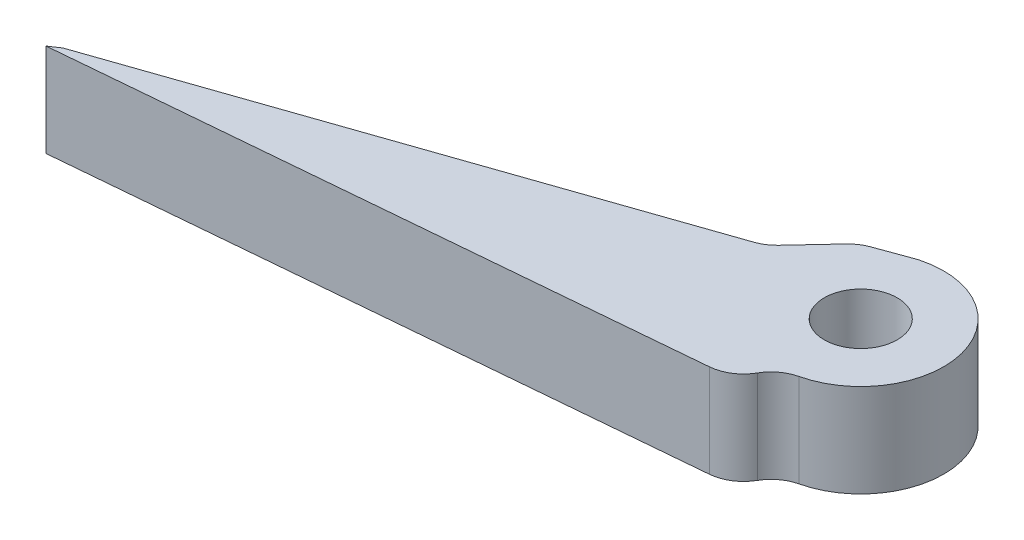
SolidWorks part; units mm, degrees
material "AISI Type A2 Tool Steel"
ref_plane "Front Plane" through (0, 0, 0) normal (0, 0, 1) x (1, 0, 0)
ref_plane "Top Plane" through (0, 0, 0) normal (0, 1, 0) x (1, 0, 0)
ref_plane "Right Plane" through (0, 0, 0) normal (1, 0, 0) x (0, 0, -1)
other "Bounding Box"
ref_plane "Default Plane" through (-8.9266, -12.7485, 0) normal (-0.1736, 0.9848, 0) x (0.9848, 0.1736, 0)
sketch "Sketch1" plane through (0, 0, 0) normal (0, 1, 0) x (1, 0, 0)
  line L0 (-1.6007, 5.4333) -> (-4.5029, 4.3739)
  line L1 (-4.5029, 4.3739) -> (-7.5661, 1.0897)
  line L2 (-7.5661, 1.0897) -> (-43.2088, -11.2108)
  line L3 (-43.2088, -11.2108) -> (-43.908, -11.6771)
  line L4 (-43.908, -11.6771) -> (0, -7.7918)
  line L5 (0, -7.7918) -> (0, -5.6642)
  circle A0 centre (0, 0) radius 2.4892
  circle A1 centre (0, 0) radius 5.6642
  dimension "D1" = 4.9784
  dimension "D3" = 3.175
  dimension "D2" = 0.8404
  dimension "D4" = 5.4333
  dimension "D5" = 4.491
  dimension "D6" = 3.0894
  dimension "D10" = 152.046
  dimension "D11" = 165.343
  dimension "D12" = 28.64
  dimension "D13" = 153.06
extrude "Boss-Extrude1" add sketch "Sketch1" along normal blind 6.35 contours A1 L0 L1 L2 L3 L4 | A1 A0 region at (3.2964, 0, -4.4077) region at (-17.05, 0, 5.9411)
fillet "Fillet1" radius 2.54 4 edges at (0, 3.175, 7.7918) (-1.6007, 3.175, -5.4333) (-4.5029, 3.175, -4.3739) (-7.5661, 3.175, -1.0897)
fillet "Fillet2" radius 2.54 1 edges at (0, 3.175, 5.6642)
